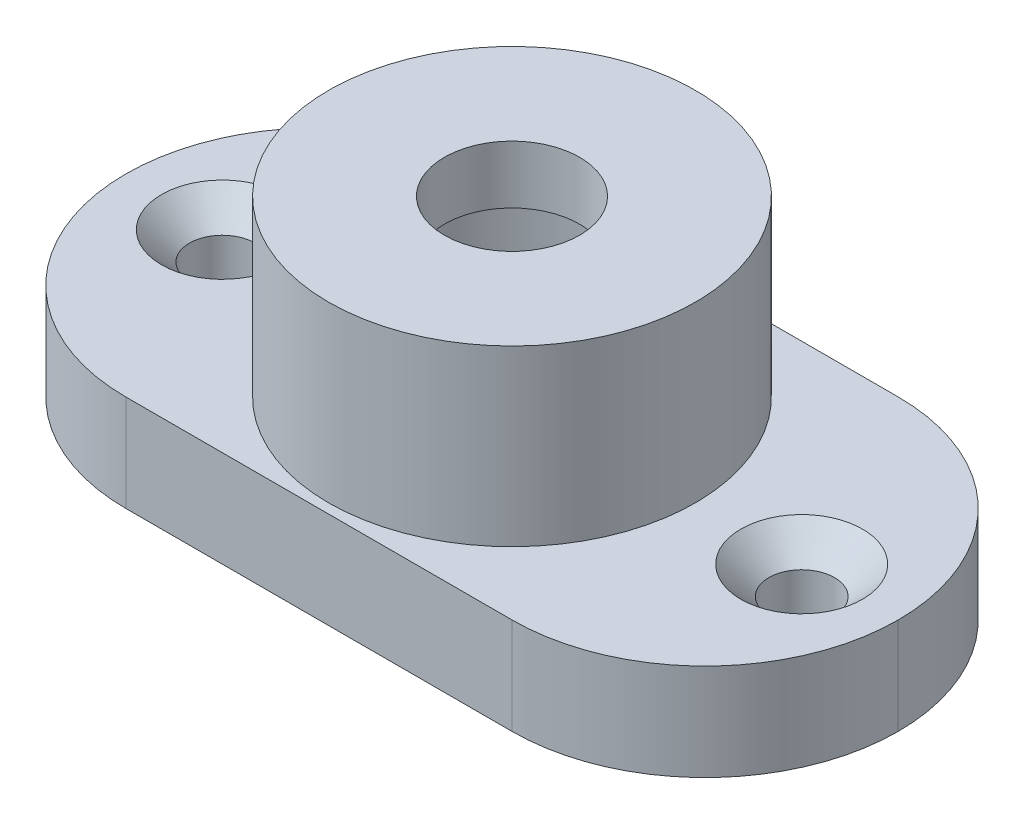
SolidWorks part; units mm, degrees
material "ABS PC"
ref_plane "Front Plane" through (0, 0, 0) normal (0, 0, 1) x (1, 0, 0)
ref_plane "Top Plane" through (0, 0, 0) normal (0, 1, 0) x (1, 0, 0)
ref_plane "Right Plane" through (0, 0, 0) normal (1, 0, 0) x (0, 0, -1)
sketch "Sketch1" plane through (0, 0, 0) normal (0, 1, 0) x (1, 0, 0)
  line L1 (-20, -10) -> (20, -10)
  line L2 (-20, -10) -> (-20, 10)
  line L3 (-20, 10) -> (20, 10)
  line L4 (20, -10) -> (20, 10)
  line L5 (-20, -10) -> (20, 10) construction
  line L6 (-20, 10) -> (20, -10) construction
  point P0 (0, 0)
  dimension "D1" = 40
  dimension "D2" = 20
extrude "Boss-Extrude1" add sketch "Sketch1" along normal blind 5
hole_wizard "CSK for M3 Flat Head Machine Screw1" positions "Sketch2" profile "Sketch3" countersink size "M3" standard "ANSI Metric" end condition through all
sketch "Sketch2" plane through (0, 5, 0) normal (0, 1, 0) x (1, 0, 0)
  line L0 (0, 0) -> (-15, 0) construction
  line L1 (0, 10) -> (0, -10) construction
  line L2 (20, 10) -> (-20, 10) construction
  line L3 (-20, -10) -> (20, -10) construction
  point P1 (-15, 0)
  point P14 (15, 0)
  dimension "D1" = 30
sketch "Sketch3" plane through (15, 5, 0) normal (1, 0, 0) x (0, 0, 1)
  line L0 (0, 0) -> (0, 5)
  line L1 (0, 5) -> (1.7, 5)
  line L2 (1.7, 5) -> (1.7, 1.45)
  line L3 (1.7, 1.45) -> (3.15, 0)
  line L5 (3.15, 0) -> (0, 0)
  line L6 (-1.7, 1.45) -> (-3.15, 0) construction
  line L11 (0, -6.35) -> (0, 107.95) construction
  dimension "Thru Hole Dia." = 3.4
  dimension "Thru Hole Depth" = 5
  dimension "Near C'Sink Dia." = 6.3
  dimension "Near C'Sink Angle" = 90
sketch "Sketch4" plane through (0, 5, 0) normal (0, 1, 0) x (1, 0, 0)
  circle A0 centre (0, 0) radius 3.5
  dimension "D1" = 7
extrude "Cut-Extrude1" cut sketch "Sketch4" against normal blind 5
sketch "Sketch5" plane through (0, 5, 0) normal (0, 1, 0) x (1, 0, 0)
  circle A2 centre (0, 0) radius 9.5
  circle A3 centre (0, 0) radius 9.5
  circle A5 centre (0, 0) radius 3.5
  circle A6 centre (0, 0) radius 3.5
  dimension "D1" = 6
  dimension "D2" = 0
extrude "Boss-Extrude2" add sketch "Sketch5" along normal blind 20
fillet "Fillet1" radius 10 4 edges at (20, 2.5, 10) (-20, 2.5, -10) (20, 2.5, -10) (-20, 2.5, 10)
sketch "Sketch6" plane through (0, 25, 0) normal (0, 1, 0) x (1, 0, 0)
  circle A1 centre (0, 0) radius 6
  circle A2 centre (0, 0) radius 3.5
  circle A3 centre (0, 0) radius 3.5
  dimension "D2" = 12
  dimension "D1" = 0
extrude "Cut-Extrude2" cut sketch "Sketch6" against normal blind 11
sketch "Sketch7" plane through (0, 0, 0) normal (0, -1, 0) x (1, 0, 0)
  circle A0 centre (0, 0) radius 8
  dimension "D1" = 16
extrude "Cut-Extrude3" cut sketch "Sketch7" against normal offset from surface (11 mm away) 3 up to face at (0, 14, 3.5)
sketch "Sketch8" plane through (0, 25, 0) normal (0, 1, 0) x (1, 0, 0)
  circle A0 centre (0, 0) radius 9.5
extrude "Cut-Extrude4" cut sketch "Sketch8" against normal up to surface (11 mm away) up to face at (0, 14, 3.5)
